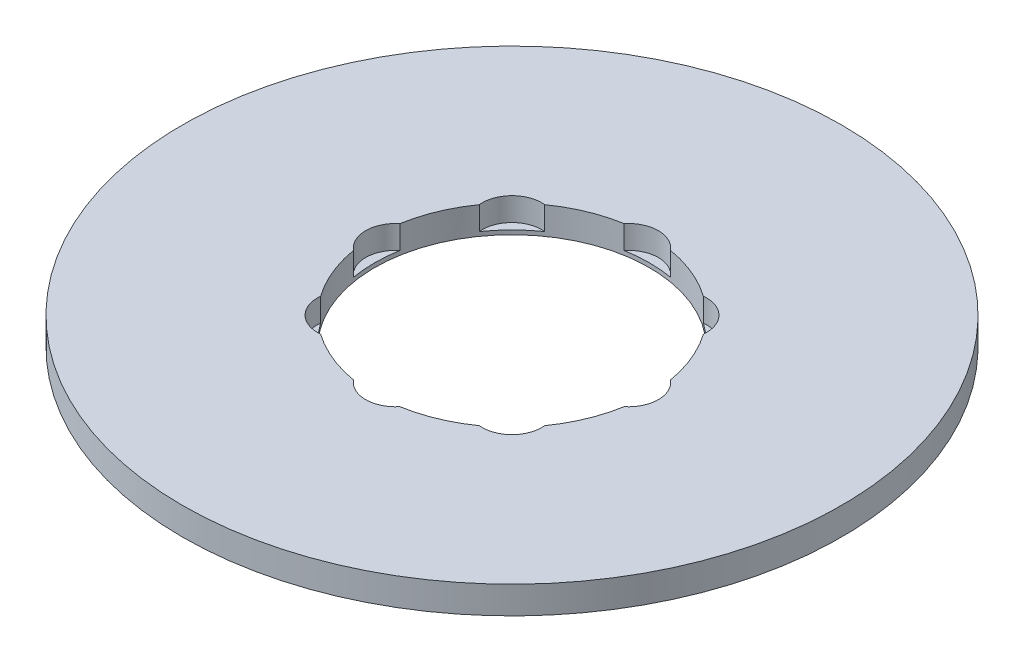
SolidWorks part; units mm, degrees
ref_plane "Front Plane" through (0, 0, 0) normal (0, 0, 1) x (1, 0, 0)
ref_plane "Top Plane" through (0, 0, 0) normal (0, 1, 0) x (1, 0, 0)
ref_plane "Right Plane" through (0, 0, 0) normal (1, 0, 0) x (0, 0, -1)
sketch "Sketch1" plane through (0, 0, 0) normal (0, 1, 0) x (1, 0, 0)
  circle A0 centre (0, 0) radius 60
  dimension "FLANGE_OD" = 120
extrude "Boss-Extrude1" add sketch "Sketch1" along normal blind 5
sketch "Sketch2" plane through (0, 0, 0) normal (0, 1, 0) x (1, 0, 0)
  circle A0 centre (0, 0) radius 25
  dimension "BORE_D" = 50
extrude "Cut-Extrude1" cut sketch "Sketch2" along normal through all
sketch "Sketch3" plane through (0, 5, 0) normal (0, 1, 0) x (1, 0, 0)
  circle A0 centre (0, 0) radius 21.2127 construction
  circle A1 centre (-21.2127, 0) radius 5.4332
  dimension "BOLT_D" = 10.8663
  dimension "BOLT_PCD" = 42.4255
extrude "Cut-Extrude2" cut sketch "Sketch3" against normal blind 4.2379
pattern_circular "CirPattern1" count 8 over 360 about axis through (0, 0, 0) along (0, 1, 0) of "Cut-Extrude2"
